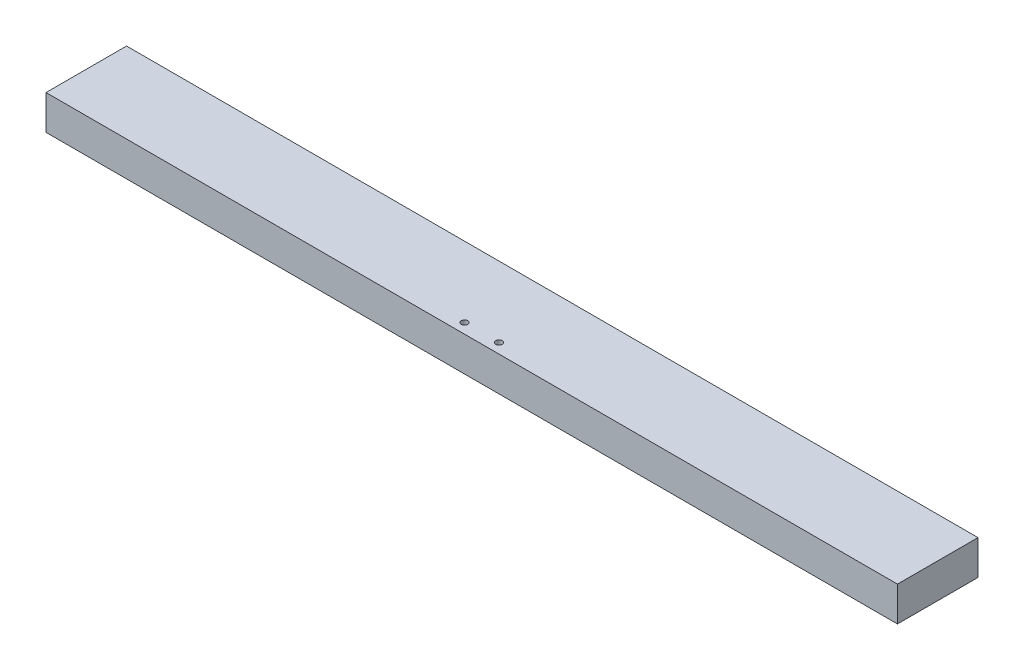
SolidWorks part; units mm, degrees
ref_plane "Front Plane" through (0, 0, 0) normal (0, 0, 1) x (1, 0, 0)
ref_plane "Top Plane" through (0, 0, 0) normal (0, 1, 0) x (1, 0, 0)
ref_plane "Right Plane" through (0, 0, 0) normal (1, 0, 0) x (0, 0, -1)
sketch "Sketch1" plane through (0, 0, 0) normal (0, 0, 1) x (1, 0, 0)
  line L1 (-469.8492, -19.05) -> (469.8492, -19.05)
  line L2 (-469.8492, -19.05) -> (-469.8492, 19.05)
  line L3 (-469.8492, 19.05) -> (469.8492, 19.05)
  line L4 (469.8492, -19.05) -> (469.8492, 19.05)
  line L5 (-469.8492, -19.05) -> (469.8492, 19.05) construction
  line L6 (-469.8492, 19.05) -> (469.8492, -19.05) construction
  point P0 (0, 0)
  dimension "D1" = 38.1
  dimension "D2" = 939.6984
extrude "Boss-Extrude1" add sketch "Sketch1" along normal blind 88.9
sketch "Sketch2" plane through (0, 19.05, 0) normal (0, 1, 0) x (1, 0, 0)
  line L0 (0, 0) -> (0, -88.9) construction
  line L1 (469.8492, 0) -> (-469.8492, 0) construction
  line L2 (469.8492, -88.9) -> (-469.8492, -88.9) construction
  line L4 (-28.575, -85.725) -> (28.575, -85.725)
  line L5 (-28.575, -85.725) -> (-28.575, -69.85)
  line L6 (-28.575, -69.85) -> (28.575, -69.85)
  line L7 (28.575, -85.725) -> (28.575, -69.85)
  line L8 (-28.575, -85.725) -> (28.575, -69.85) construction
  line L9 (-28.575, -69.85) -> (28.575, -85.725) construction
  circle A0 centre (-19.05, -77.7875) radius 3.5719
  circle A1 centre (19.05, -77.7875) radius 3.5719
  point P6 (0, -77.7875)
  dimension "D5" = 7.1437
  dimension "D6" = 7.1437
  dimension "D1" = 15.875
  dimension "D2" = 57.15
  dimension "D3" = 19.05
  dimension "D4" = 19.05
  dimension "D7" = 7.9375
  dimension "D8" = 7.9375
  dimension "D9" = 69.85
extrude "Cut-Extrude1" cut sketch "Sketch2" against normal through all contours A1 | A0 region at (19.05, 19.05, 77.7875)
